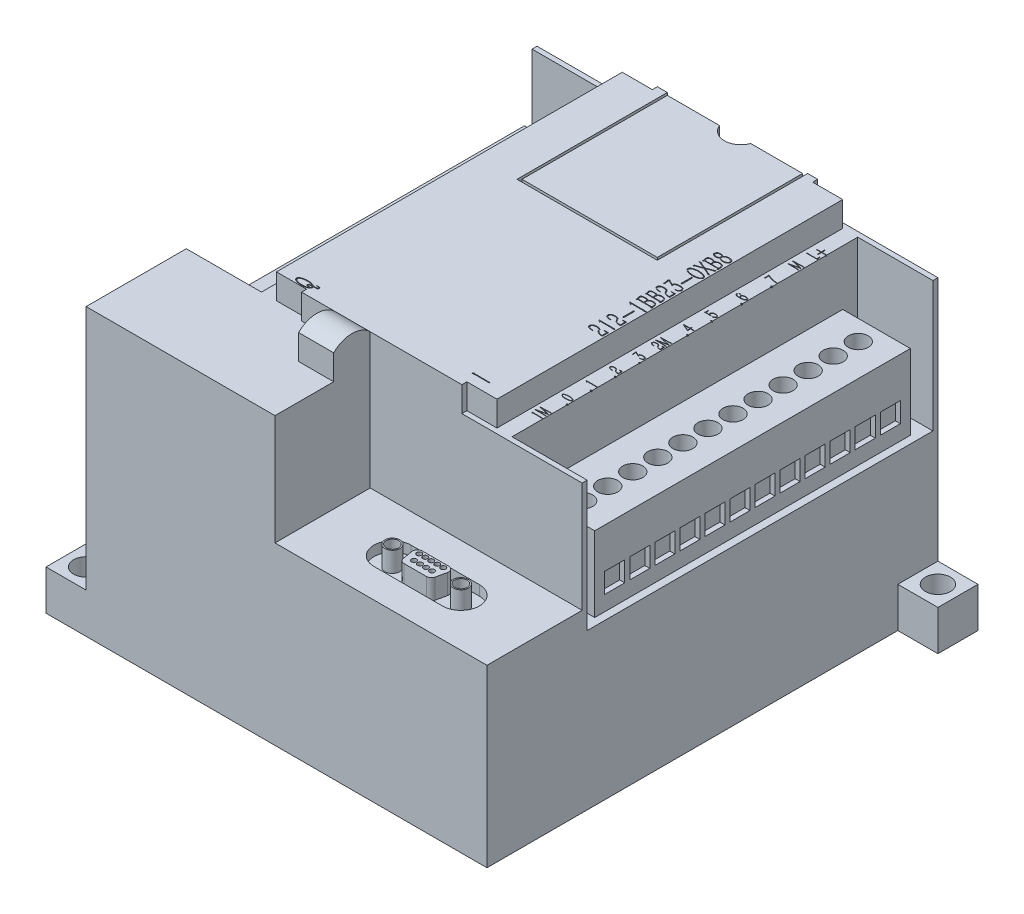
SolidWorks part; units mm, degrees
ref_plane "前视基准面" through (0, 0, 0) normal (0, 0, 1) x (1, 0, 0)
ref_plane "上视基准面" through (0, 0, 0) normal (0, 1, 0) x (1, 0, 0)
ref_plane "右视基准面" through (0, 0, 0) normal (1, 0, 0) x (0, 0, -1)
sketch "草图1" plane through (0, 0, 0) normal (0, 1, 0) x (1, 0, 0)
  line L1 (-40, 45) -> (40, 45)
  line L2 (-40, 45) -> (-40, -45)
  line L3 (-40, -45) -> (40, -45)
  line L4 (40, 45) -> (40, -45)
  line L5 (-40, 45) -> (40, -45) construction
  line L6 (-40, -45) -> (40, 45) construction
  point P0 (0, 0)
  dimension "D1" = 80
  dimension "D2" = 90
extrude "凸台-拉伸1" add sketch "草图1" along normal blind 62
sketch "草图2" plane through (0, 62, 0) normal (0, 1, 0) x (1, 0, 0)
  line L0 (-40, -26) -> (40, -26)
  line L1 (-40, 45) -> (-40, -45) construction
  line L2 (40, -45) -> (40, 45) construction
  line L3 (40, -26) -> (40, -45)
  line L4 (40, -45) -> (-40, -45)
  line L5 (-40, -45) -> (-40, -26)
  dimension "D1" = 19
extrude "切除-拉伸1" cut sketch "草图2" against normal blind 5
sketch "草图3" plane through (0, 57, 0) normal (0, 1, 0) x (1, 0, 0)
  line L0 (-2.3, -26) -> (-2.3, -45)
  line L1 (40, -26) -> (-40, -26) construction
  line L2 (-40, -45) -> (40, -45) construction
  line L3 (-2.3, -45) -> (40, -45)
  line L4 (40, -45) -> (40, -26)
  line L5 (40, -26) -> (-2.3, -26)
  line L6 (-40, -26) -> (-40, -45) construction
  dimension "D1" = 37.7
extrude "切除-拉伸2" cut sketch "草图3" against normal blind 22
sketch "草图4" plane through (0, 0, 0) normal (0, -1, 0) x (1, 0, 0)
  line L1 (-40, 45) -> (-48, 45)
  line L2 (-40, 45) -> (-40, 37)
  line L3 (-40, 37) -> (-48, 37)
  line L4 (-48, 45) -> (-48, 37)
  line L5 (40, -45) -> (48, -45)
  line L6 (40, -45) -> (40, -37)
  line L7 (40, -37) -> (48, -37)
  line L8 (48, -45) -> (48, -37)
  circle A0 centre (-44, 41) radius 2.5
  circle A1 centre (44, -41) radius 2.5
  dimension "D5" = 5
  dimension "D6" = 5
  dimension "D1" = 8
  dimension "D2" = 8
  dimension "D3" = 8
  dimension "D4" = 8
extrude "凸台-拉伸2" add sketch "草图4" against normal blind 8
sketch "草图5" plane through (0, 62, 0) normal (0, 1, 0) x (1, 0, 0)
  line L0 (16, -26) -> (40, -26)
  line L1 (40, -26) -> (-40, -26) construction
  line L2 (40, -26) -> (40, 45)
  line L3 (40, 45) -> (16, 45)
  line L4 (40, 45) -> (-40, 45) construction
  line L5 (16, 45) -> (16, 44)
  line L6 (16, 44) -> (22, 44)
  line L7 (22, 44) -> (22, -25)
  line L8 (22, -25) -> (16, -25)
  line L9 (16, -25) -> (16, -26)
  line L12 (-14, 45) -> (-14, 15)
  line L13 (14, 45) -> (14, 15)
  line L14 (-13.5, 44.5) -> (-3.0716, 44.5)
  line L15 (13.5, 44.5) -> (13.5, 15.5)
  line L16 (-14, 45) -> (14, 45)
  line L17 (-14, 15) -> (14, 15)
  line L18 (-13.5, 15.5) -> (13.5, 15.5)
  line L19 (-13.5, 44.5) -> (-13.5, 15.5)
  line L20 (-40, -26) -> (-40, 45)
  line L21 (3.1365, 44.5) -> (13.5, 44.5)
  line L22 (-40, -26) -> (40, -26)
  line L23 (40, -26) -> (40, 45)
  line L24 (40, 45) -> (-40, 45)
  line L25 (-40, 45) -> (-40, -26)
  line L26 (-40, -26) -> (40, -26)
  line L27 (40, -26) -> (40, 45)
  line L28 (40, 45) -> (-40, 45)
  line L29 (-40, 45) -> (-40, -26)
  line L30 (-13.5, 44.5) -> (13.5, 44.5) construction
  line L31 (-16, -25) -> (-16, -26)
  line L32 (-22, -25) -> (-16, -25)
  line L33 (-22, 44) -> (-22, -25)
  line L34 (-16, 44) -> (-22, 44)
  line L35 (-16, 45) -> (-16, 44)
  line L36 (-40, 45) -> (-16, 45)
  line L38 (-16, -26) -> (-40, -26)
  arc A1 (-3.0716, 44.5) -> (3.1365, 44.5) centre (0.0325, 45.6546) ccw
  point P31 (-3.1884, 44.8836)
  point P32 (3.2533, 44.8836)
  line M5 (-40, -26) -> (40, -26)
  line M6 (40, -26) -> (40, 45)
  line M7 (40, 45) -> (-40, 45)
  line M8 (-40, 45) -> (-40, -26)
  dimension "D1" = 1
  dimension "D2" = 1
  dimension "D3" = 24
  dimension "D4" = 24
  dimension "D5" = 18
  dimension "D6" = 0.5
  dimension "D8" = 0
  dimension "D9" = 30
extrude "切除-拉伸3" cut sketch "草图5" against normal blind 5 contours L35 L28 L31 L32 L33 L34 M8 M5 | L8 L9 L5 L6 L7 M5 M6 M7 | L30 A1 | L12 L17 L13 L14 L30 L21 L15 L18 L19 M7 region at (30.8884, 62, -9.5) region at (-30.8884, 62, -9.5) region at (13.5896, 62, -30) region at (0.0325, 62, -43.6073)
sketch "草图6" plane through (0, 57, 0) normal (0, 1, 0) x (1, 0, 0)
  line L0 (25, 44) -> (40, 44)
  line L1 (40, -26) -> (40, 45) construction
  line L2 (40, 44) -> (40, -25)
  line L3 (25, -23.7723) -> (25, -25)
  line L4 (25, -23.7723) -> (25, 44)
  line L5 (22, 44) -> (22, -25) construction
  line L6 (25, -25) -> (40, -25)
  dimension "D1" = 3
extrude "切除-拉伸4" cut sketch "草图6" against normal blind 11
sketch "草图7" plane through (0, 46, 0) normal (0, 1, 0) x (1, 0, 0)
  line L0 (25, 44) -> (25, 41)
  line L1 (25, 44) -> (25, -25) construction
  line L2 (25, 41) -> (40, 41)
  line L3 (40, 37) -> (40, 45) construction
  line L4 (40, 41) -> (40, 44)
  line L5 (40, 44) -> (25, 44)
  line L6 (25, -25) -> (25, -22)
  line L7 (25, -22) -> (40, -22)
  line L8 (40, -25) -> (40, 44) construction
  line L9 (40, -22) -> (40, -25)
  line L10 (25, -25) -> (40, -25) construction
  line L11 (40, -25) -> (25, -25)
  line L12 (38.5, 41) -> (38.5, -22)
  circle A0 centre (32.1039, 37) radius 2
  circle A1 centre (32.1039, 32) radius 2
  circle A2 centre (32.1039, 27) radius 2
  circle A3 centre (32.1039, 22) radius 2
  circle A4 centre (32.1039, 17) radius 2
  circle A5 centre (32.1039, 12) radius 2
  circle A6 centre (32.1039, 7) radius 2
  circle A7 centre (32.1039, 2) radius 2
  circle A8 centre (32.1039, -3) radius 2
  circle A9 centre (32.1039, -8) radius 2
  circle A10 centre (32.1039, -13) radius 2
  circle A11 centre (32.1039, -18) radius 2
  line M13 (25, 44) -> (25, -25)
  line M14 (25, -25) -> (40, -25)
  line M15 (40, -25) -> (40, 44)
  line M16 (40, 44) -> (25, 44)
  dimension "D4" = 4
  dimension "D1" = 3
  dimension "D2" = 3
  dimension "D3" = 1.5
  dimension "D5" = 4
  dimension "D6" = 12
extrude "切除-拉伸5" cut sketch "草图7" against normal blind 15 contours A8 | A7 | A6 | A5 | A4 | A9 | A10 | A11 | A1 | A3 | A2 | L2 M13 M15 M16 | A0 | L2 L12 L7 M15 | L7 M13 M14 M15 | A2 | A0 region at (32.5, 46, -42.5) region at (39.25, 46, -9.5) region at (32.5, 46, 23.5) region at (32.1039, 46, -37) region at (32.1039, 46, -32) region at (32.1039, 46, -27) region at (32.1039, 46, -22) region at (32.1039, 46, -17) region at (32.1039, 46, -12) region at (32.1039, 46, -7) region at (32.1039, 46, -2) region at (32.1039, 46, 3) region at (32.1039, 46, 8) region at (32.1039, 46, 13) region at (32.1039, 46, 18)
sketch "草图9" plane through (38.5, 0, 0) normal (1, 0, 0) x (0, 0, -1)
  line L0 (41, 31) -> (41, 46) construction
  line L1 (35, 38) -> (39, 38)
  line L2 (35, 38) -> (35, 34)
  line L3 (35, 34) -> (39, 34)
  line L4 (39, 38) -> (39, 34)
  line L5 (41, 31) -> (-22, 31) construction
  line L6 (30, 38) -> (34, 38)
  line L7 (34, 38) -> (34, 34)
  line L8 (30, 34) -> (34, 34)
  line L9 (30, 38) -> (30, 34)
  line L10 (25, 38) -> (29, 38)
  line L11 (29, 38) -> (29, 34)
  line L12 (25, 34) -> (29, 34)
  line L13 (25, 38) -> (25, 34)
  line L14 (20, 38) -> (24, 38)
  line L15 (24, 38) -> (24, 34)
  line L16 (20, 34) -> (24, 34)
  line L17 (20, 38) -> (20, 34)
  line L18 (15, 38) -> (19, 38)
  line L19 (19, 38) -> (19, 34)
  line L20 (15, 34) -> (19, 34)
  line L21 (15, 38) -> (15, 34)
  line L22 (10, 38) -> (14, 38)
  line L23 (14, 38) -> (14, 34)
  line L24 (10, 34) -> (14, 34)
  line L25 (10, 38) -> (10, 34)
  line L26 (5, 38) -> (9, 38)
  line L27 (9, 38) -> (9, 34)
  line L28 (5, 34) -> (9, 34)
  line L29 (5, 38) -> (5, 34)
  line L30 (0, 38) -> (4, 38)
  line L31 (4, 38) -> (4, 34)
  line L32 (0, 34) -> (4, 34)
  line L33 (0, 38) -> (0, 34)
  line L34 (-5, 38) -> (-1, 38)
  line L35 (-1, 38) -> (-1, 34)
  line L36 (-5, 34) -> (-1, 34)
  line L37 (-5, 38) -> (-5, 34)
  line L38 (-10, 38) -> (-6, 38)
  line L39 (-6, 38) -> (-6, 34)
  line L40 (-10, 34) -> (-6, 34)
  line L41 (-10, 38) -> (-10, 34)
  line L42 (-15, 38) -> (-11, 38)
  line L43 (-11, 38) -> (-11, 34)
  line L44 (-15, 34) -> (-11, 34)
  line L45 (-15, 38) -> (-15, 34)
  line L46 (-20, 38) -> (-16, 38)
  line L47 (-16, 38) -> (-16, 34)
  line L48 (-20, 34) -> (-16, 34)
  line L49 (-20, 38) -> (-20, 34)
  dimension "D1" = 2
  dimension "D2" = 4
  dimension "D3" = 4
  dimension "D4" = 3
extrude "切除-拉伸6" cut sketch "草图9" against normal blind 1
sketch "草图10" plane through (0, 35, 0) normal (0, 1, 0) x (1, 0, 0)
  line L0 (11.6371, -35.5) -> (25.3018, -35.5) construction
  line L1 (11.6371, -31.8082) -> (25.3018, -31.8082)
  line L2 (11.6371, -39.1918) -> (25.3018, -39.1918)
  line L3 (40, -26) -> (-2.3, -26) construction
  arc A0 (11.6371, -31.8082) -> (11.6371, -39.1918) centre (11.6371, -35.5) ccw
  arc A1 (25.3018, -39.1918) -> (25.3018, -31.8082) centre (25.3018, -35.5) ccw
  point P2 (18.4694, -35.5)
  dimension "D1" = 9.5
extrude "切除-拉伸7" cut sketch "草图10" against normal blind 2
sketch "草图11" plane through (0, 33, 0) normal (0, 1, 0) x (1, 0, 0)
  line L0 (14.6371, -33.6883) -> (15.3392, -37.6883)
  line L1 (14.6371, -33.6883) -> (22.3018, -33.6883)
  line L3 (15.3392, -37.6883) -> (21.4, -37.6883)
  line L5 (22.3018, -33.6883) -> (21.4, -37.6883)
  circle A0 centre (11.6371, -35.5) radius 1.5
  circle A1 centre (25.3018, -35.5) radius 1.5
  dimension "D1" = 3
  dimension "D2" = 3
  dimension "D5" = 4
extrude "凸台-拉伸3" add sketch "草图11" along normal blind 4
fillet "圆角1" radius 1 4 edges at (14.6371, 35, 33.6883) (22.3018, 35, 33.6883) (21.4, 35, 37.6883) (15.3392, 35, 37.6883)
sketch "草图12" plane through (0, 37, 0) normal (0, 1, 0) x (1, 0, 0)
  line L0 (14.843, -34.8611) -> (15.194, -36.8611) construction
  circle A0 centre (11.6371, -35.5) radius 1.25
  circle A1 centre (25.3018, -35.5) radius 1.25
  circle A2 centre (15.971, -34.4879) radius 0.5
  circle A3 centre (16.594, -36.161) radius 0.5
  circle A4 centre (17.171, -34.4879) radius 0.5
  circle A5 centre (18.371, -34.4879) radius 0.5
  circle A6 centre (19.571, -34.4879) radius 0.5
  circle A7 centre (20.771, -34.4879) radius 0.5
  circle A8 centre (17.794, -36.161) radius 0.5
  circle A9 centre (18.994, -36.161) radius 0.5
  circle A10 centre (20.194, -36.161) radius 0.5
  dimension "D1" = 2.5
  dimension "D2" = 2.5
  dimension "D3" = 1
  dimension "D4" = 1
  dimension "D5" = 1.5
extrude "切除-拉伸8" cut sketch "草图12" against normal blind 2
sketch "草图13" plane through (-2.3, 0, 0) normal (1, 0, 0) x (0, 0, -1)
  line L0 (-33.2887, 62.0016) -> (-26, 62.0016)
  line L1 (-26, 57) -> (-33.2887, 57)
  line L2 (-26, 57) -> (-26, 62.0016)
  line L3 (-26, 62.0016) -> (-33.2887, 62.0016)
  line L4 (-33.2887, 57) -> (-33.2887, 62.0016)
  arc A0 (-26, 62.0016) -> (-33.2887, 62.0016) centre (-29.6444, 58.3572) ccw
  line M1 (-26, 57) -> (-45, 57)
extrude "凸台-拉伸4" add sketch "草图13" against normal blind 7 contours L4 L2 L0 M1 | L0 A0 region at (-2.3, 62.6137, 29.6444) region at (-2.3, 59.5008, 29.6444)
sketch "草图14" plane through (37.5, 0, 0) normal (1, 0, 0) x (0, 0, -1)
  point P0 (-18, 36)
  point P1 (-13, 36)
  point P2 (-8, 36)
  point P3 (-3, 36)
  point P4 (2, 36)
  point P5 (7, 36)
  point P6 (12, 36)
  point P7 (17, 36)
  point P8 (22, 36)
  point P9 (27, 36)
  point P10 (32, 36)
  point P11 (37, 36)
mirror "镜向2" about plane through (0, 0, 0) normal (1, 0, 0) of "切除-拉伸6", "切除-拉伸4", "切除-拉伸5"
sketch "草图15" plane through (-37.5, 0, 0) normal (-1, 0, 0) x (0, 0, 1)
  point P0 (-37, 36)
  point P1 (-27, 36)
  point P3 (-32, 36)
  point P5 (-22, 36)
  point P7 (-17, 36)
  point P9 (-12, 36)
  point P11 (-7, 36)
  point P13 (-2, 36)
  point P15 (3, 36)
  point P17 (8, 36)
  point P19 (13, 36)
  point P21 (18, 36)
sketch "草图17" plane through (0, 57, 0) normal (0, 1, 0) x (1, 0, 0)
  text T0 "1M  .0  .1  .2  .3  2M  .4  .5   .6   .7   M  L+  " font "汉仪长仿宋体" height in points 9
  text T1 "1L   .0  .1   .2  · 2L   .3   .4  .5   PE  N   L1 AC  " font "汉仪长仿宋体" height in points 9
extrude "切除-拉伸9" cut sketch "草图17" against normal blind 0.2
sketch "草图18" plane through (0, 62, 0) normal (0, 1, 0) x (1, 0, 0)
  text T0 "212-1BB23-OXB8"
extrude "切除-拉伸10" cut sketch "草图18" against normal blind 0.2
sketch "草图19" plane through (0, 62, 0) normal (0, 1, 0) x (1, 0, 0)
  text T0 "\r\nQ\r\n\r\n\r\n\r\n \r\n I"
extrude "切除-拉伸11" cut sketch "草图19" against normal blind 0.3
sketch "0_0_Point" plane through (-37.5, 0, 0) normal (-1, 0, 0) x (0, 0, 1)
  point P0 (18, 36)
other "0_0" parameters "直径"=2, "端头长度"=2
ref_axis "基准轴1" through (-47.5, 36, 18) along (1, 0, 0)
sketch "1_0_Point" plane through (-37.5, 0, 0) normal (-1, 0, 0) x (0, 0, 1)
  point P0 (13, 36)
other "1_0" parameters "直径"=2, "端头长度"=2
ref_axis "基准轴2" through (-47.5, 36, 13) along (1, 0, 0)
sketch "2_0_Point" plane through (-37.5, 0, 0) normal (-1, 0, 0) x (0, 0, 1)
  point P0 (8, 36)
other "2_0" parameters "直径"=2, "端头长度"=2
ref_axis "基准轴3" through (-47.5, 36, 8) along (1, 0, 0)
sketch "3_0_Point" plane through (-37.5, 0, 0) normal (-1, 0, 0) x (0, 0, 1)
  point P0 (3, 36)
other "3_0" parameters "直径"=2, "端头长度"=2
ref_axis "基准轴4" through (-47.5, 36, 3) along (1, 0, 0)
sketch "4_0_Point" plane through (-37.5, 0, 0) normal (-1, 0, 0) x (0, 0, 1)
  point P0 (-2, 36)
other "4_0" parameters "直径"=2, "端头长度"=2
ref_axis "基准轴5" through (-47.5, 36, -2) along (1, 0, 0)
sketch "5_0_Point" plane through (-37.5, 0, 0) normal (-1, 0, 0) x (0, 0, 1)
  point P0 (-7, 36)
other "5_0" parameters "直径"=2, "端头长度"=2
ref_axis "基准轴6" through (-47.5, 36, -7) along (1, 0, 0)
sketch "6_0_Point" plane through (-37.5, 0, 0) normal (-1, 0, 0) x (0, 0, 1)
  point P0 (-12, 36)
other "6_0" parameters "直径"=2, "端头长度"=2
ref_axis "基准轴7" through (-47.5, 36, -12) along (1, 0, 0)
sketch "7_0_Point" plane through (-37.5, 0, 0) normal (-1, 0, 0) x (0, 0, 1)
  point P0 (-17, 36)
other "7_0" parameters "直径"=2, "端头长度"=2
ref_axis "基准轴8" through (-47.5, 36, -17) along (1, 0, 0)
sketch "8_0_Point" plane through (-37.5, 0, 0) normal (-1, 0, 0) x (0, 0, 1)
  point P0 (-22, 36)
other "8_0" parameters "直径"=2, "端头长度"=2
ref_axis "基准轴9" through (-47.5, 36, -22) along (1, 0, 0)
sketch "9_0_Point" plane through (-37.5, 0, 0) normal (-1, 0, 0) x (0, 0, 1)
  point P0 (-27, 36)
other "9_0" parameters "直径"=2, "端头长度"=2
ref_axis "基准轴10" through (-47.5, 36, -27) along (1, 0, 0)
sketch "10_0_Point" plane through (-37.5, 0, 0) normal (-1, 0, 0) x (0, 0, 1)
  point P0 (-32, 36)
other "10_0" parameters "直径"=2, "端头长度"=2
ref_axis "基准轴11" through (-47.5, 36, -32) along (1, 0, 0)
sketch "11_0_Point" plane through (-37.5, 0, 0) normal (-1, 0, 0) x (0, 0, 1)
  point P0 (-37, 36)
other "11_0" parameters "直径"=2, "端头长度"=2
ref_axis "基准轴12" through (-47.5, 36, -37) along (1, 0, 0)
sketch "12_0_Point" plane through (37.5, 0, 0) normal (1, 0, 0) x (0, 0, -1)
  point P0 (-18, 36)
other "12_0" parameters "直径"=2, "端头长度"=2
ref_axis "基准轴13" through (47.5, 36, 18) along (-1, 0, 0)
sketch "13_0_Point" plane through (37.5, 0, 0) normal (1, 0, 0) x (0, 0, -1)
  point P0 (-13, 36)
other "13_0" parameters "直径"=2, "端头长度"=2
ref_axis "基准轴14" through (47.5, 36, 13) along (-1, 0, 0)
sketch "14_0_Point" plane through (37.5, 0, 0) normal (1, 0, 0) x (0, 0, -1)
  point P0 (-8, 36)
other "14_0" parameters "直径"=2, "端头长度"=2
ref_axis "基准轴15" through (47.5, 36, 8) along (-1, 0, 0)
sketch "15_0_Point" plane through (37.5, 0, 0) normal (1, 0, 0) x (0, 0, -1)
  point P0 (-3, 36)
other "15_0" parameters "直径"=2, "端头长度"=2
ref_axis "基准轴16" through (47.5, 36, 3) along (-1, 0, 0)
sketch "16_0_Point" plane through (37.5, 0, 0) normal (1, 0, 0) x (0, 0, -1)
  point P0 (2, 36)
other "16_0" parameters "直径"=2, "端头长度"=2
ref_axis "基准轴17" through (47.5, 36, -2) along (-1, 0, 0)
sketch "17_0_Point" plane through (37.5, 0, 0) normal (1, 0, 0) x (0, 0, -1)
  point P0 (7, 36)
other "17_0" parameters "直径"=2, "端头长度"=2
ref_axis "基准轴18" through (47.5, 36, -7) along (-1, 0, 0)
sketch "18_0_Point" plane through (37.5, 0, 0) normal (1, 0, 0) x (0, 0, -1)
  point P0 (12, 36)
other "18_0" parameters "直径"=2, "端头长度"=2
ref_axis "基准轴19" through (47.5, 36, -12) along (-1, 0, 0)
sketch "19_0_Point" plane through (37.5, 0, 0) normal (1, 0, 0) x (0, 0, -1)
  point P0 (17, 36)
other "19_0" parameters "直径"=2, "端头长度"=2
ref_axis "基准轴20" through (47.5, 36, -17) along (-1, 0, 0)
sketch "20_0_Point" plane through (37.5, 0, 0) normal (1, 0, 0) x (0, 0, -1)
  point P0 (22, 36)
other "20_0" parameters "直径"=2, "端头长度"=2
ref_axis "基准轴21" through (47.5, 36, -22) along (-1, 0, 0)
sketch "21_0_Point" plane through (37.5, 0, 0) normal (1, 0, 0) x (0, 0, -1)
  point P0 (27, 36)
other "21_0" parameters "直径"=2, "端头长度"=2
ref_axis "基准轴22" through (47.5, 36, -27) along (-1, 0, 0)
sketch "22_0_Point" plane through (37.5, 0, 0) normal (1, 0, 0) x (0, 0, -1)
  point P0 (32, 36)
other "22_0" parameters "直径"=2, "端头长度"=2
ref_axis "基准轴23" through (47.5, 36, -32) along (-1, 0, 0)
sketch "23_0_Point" plane through (37.5, 0, 0) normal (1, 0, 0) x (0, 0, -1)
  point P0 (37, 36)
other "23_0" parameters "直径"=2, "端头长度"=2
ref_axis "基准轴24" through (47.5, 36, -37) along (-1, 0, 0)
